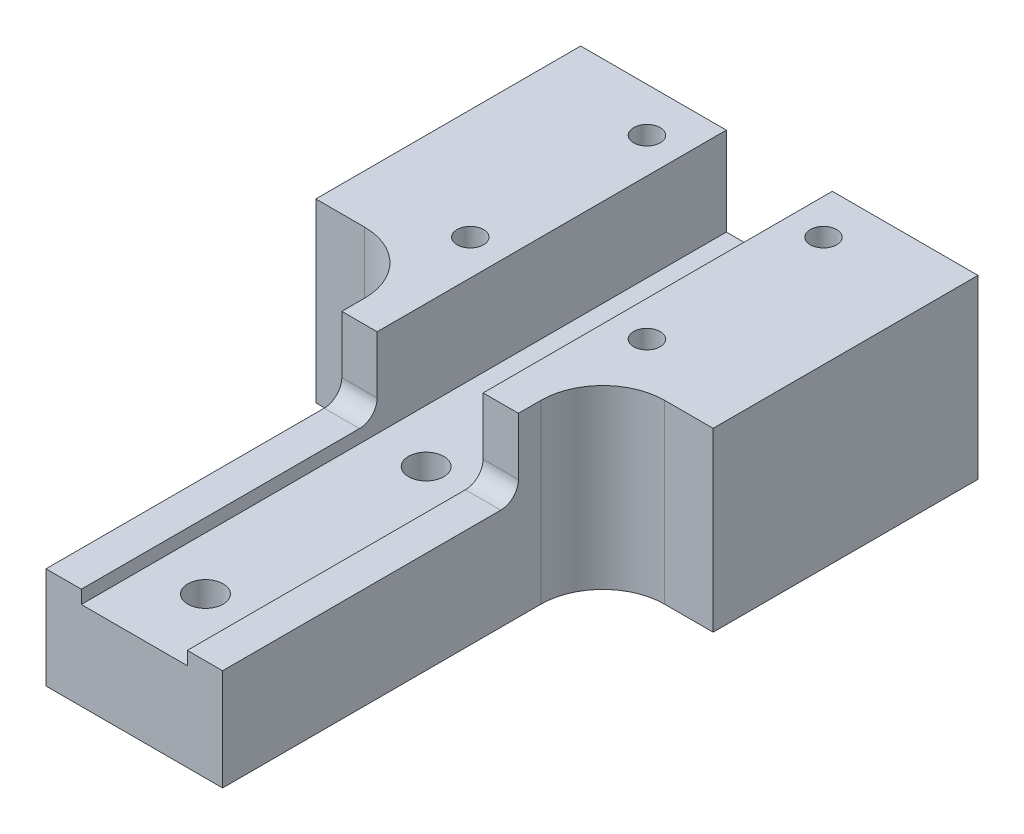
SolidWorks part; units mm, degrees
ref_plane "Front Plane" through (0, 0, 0) normal (0, 0, 1) x (1, 0, 0)
ref_plane "Top Plane" through (0, 0, 0) normal (0, 1, 0) x (1, 0, 0)
ref_plane "Right Plane" through (0, 0, 0) normal (1, 0, 0) x (0, 0, -1)
sketch "Sketch1" plane through (0, 0, 0) normal (0, 1, 0) x (1, 0, 0)
  line L0 (0, -55) -> (0, 55) construction
  line L1 (-22.5, 15) -> (22.5, 15)
  line L2 (-22.5, 15) -> (-22.5, -15)
  line L3 (-22.5, -15) -> (22.5, -15)
  line L4 (22.5, 15) -> (22.5, -15)
  line L5 (-22.5, 15) -> (22.5, -15) construction
  line L6 (-22.5, -15) -> (22.5, 15) construction
  line L7 (-10, 10) -> (10, 10)
  line L8 (-10, 10) -> (-10, -10) construction
  line L9 (-10, -10) -> (10, -10) construction
  line L10 (10, 10) -> (10, -10) construction
  line L11 (-10, 10) -> (10, -10) construction
  line L12 (-10, -10) -> (10, 10) construction
  line L13 (-10, -15) -> (10, -15)
  line L14 (-10, -15) -> (-10, -58.0584)
  line L15 (-10, -58.0584) -> (10, -58.0584)
  line L16 (10, -15) -> (10, -58.0584)
  line L17 (0, -1000) -> (0, 49000) construction
  circle A0 centre (-10, 10) radius 1.5
  circle A1 centre (10, 10) radius 1.5
  circle A2 centre (10, -10) radius 1.5
  circle A3 centre (-10, -10) radius 1.5
  circle A4 centre (0, -25) radius 2
  circle A5 centre (0, -50) radius 2
  point P0 (0, 0)
  point P6 (0, 0)
  dimension "D1" = 3
  dimension "D9" = 40
  dimension "D6" = 25
  dimension "D8" = 4
  dimension "D2" = 45
  dimension "D3" = 20
  dimension "D4" = 20
  dimension "D5" = 30
  dimension "D7" = 20
extrude "Boss-Extrude2" add sketch "Sketch1" against normal blind 20 contours L4 L1 L2 L3 A3 A2 A1 A0 | A4 | A5 | L14 L13 L16 L15 region at (0, 0, 0) region at (0, 0, 25) region at (0, 0, 50)
sketch "Sketch5" plane through (0, 0, 0) normal (0, 1, 0) x (1, 0, 0)
  line L0 (0, -11) -> (0, 11) construction
  line L1 (-6, 33.5348) -> (6, 33.5348)
  line L2 (-6, 33.5348) -> (-6, -66.4652)
  line L3 (-6, -66.4652) -> (6, -66.4652)
  line L4 (6, 33.5348) -> (6, -66.4652)
  line L5 (-6, 33.5348) -> (6, -66.4652) construction
  line L6 (-6, -66.4652) -> (6, 33.5348) construction
  point P0 (0, -16.4652)
  dimension "D1" = 12
  dimension "D2" = 100
extrude "Cut-Extrude1" cut sketch "Sketch5" against normal blind 10
fillet "Fillet1" radius 7 2 edges at (-10, -10, 15) (10, -10, 15)
ref_plane "Plane12" through (0, -8.5, 0) normal (0, 1, 0) x (1, 0, 0)
sketch "Sketch7" plane through (0, -8.5, 0) normal (0, 1, 0) x (1, 0, 0)
  line L1 (-15.6584, -24.5529) -> (14.0386, -24.5529)
  line L2 (-15.6584, -24.5529) -> (-15.6584, -59.5414)
  line L3 (-15.6584, -59.5414) -> (14.0386, -59.5414)
  line L4 (14.0386, -24.5529) -> (14.0386, -59.5414)
  line L5 (-0.8099, -59.5414) -> (-0.8099, -24.5529) construction
  line L6 (-15.6584, -42.0471) -> (14.0386, -42.0471) construction
  point P192 (-0.8099, -42.0471)
extrude "Cut-Extrude2" cut sketch "Sketch7" along normal through all
fillet "Fillet3" radius 2 2 edges at (8, -8.5, 24.5529) (-8, -8.5, 24.5529)
